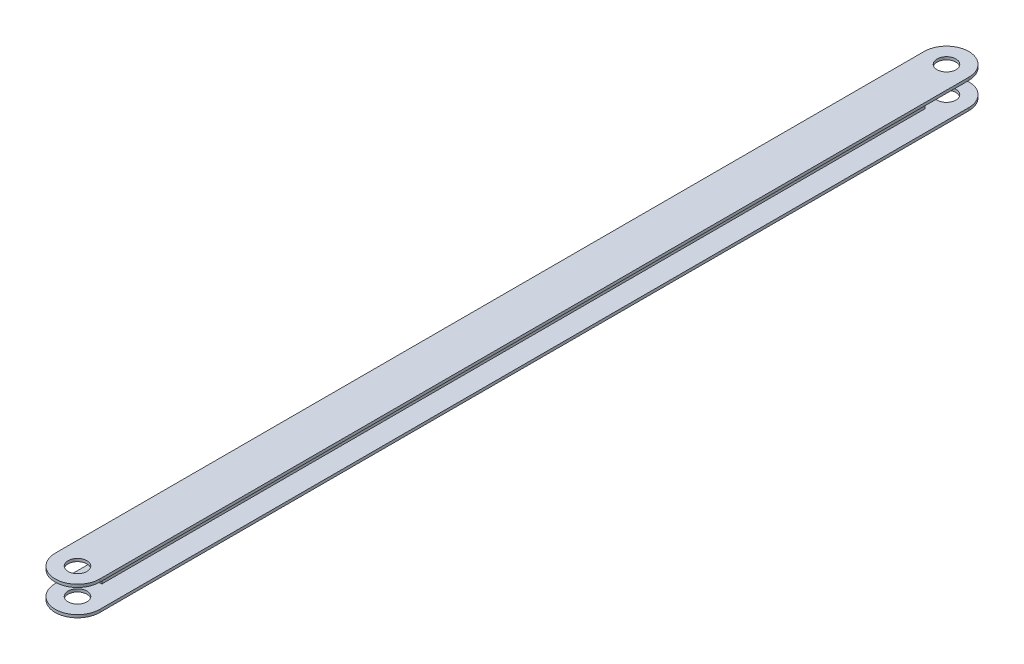
SolidWorks part; units mm, degrees
ref_plane "Front Plane" through (0, 0, 0) normal (0, 0, 1) x (1, 0, 0)
ref_plane "Top Plane" through (0, 0, 0) normal (0, 1, 0) x (1, 0, 0)
ref_plane "Right Plane" through (0, 0, 0) normal (1, 0, 0) x (0, 0, -1)
sketch "Sketch1" plane through (0, 0, 0) normal (0, 0, 1) x (1, 0, 0)
  line L0 (0, 0) -> (0, -5.6)
  line L1 (-0.6, 5) -> (0.6, 5)
  line L2 (-0.6, 5) -> (-0.6, -5)
  line L3 (-0.6, -5) -> (0.6, -5)
  line L4 (0.6, 5) -> (0.6, -5)
  line L5 (-0.6, 5) -> (0.6, -5) construction
  line L6 (-0.6, -5) -> (0.6, 5) construction
  line L7 (-9.5, -5) -> (9.5, -5)
  line L8 (-9.5, -5) -> (-9.5, -6.2)
  line L9 (-9.5, -6.2) -> (9.5, -6.2)
  line L10 (9.5, -5) -> (9.5, -6.2)
  line L11 (-9.5, -5) -> (9.5, -6.2) construction
  line L12 (-9.5, -6.2) -> (9.5, -5) construction
  line L13 (0, 0) -> (6.3315, 0) construction
  line L14 (-9.5, 6.2) -> (9.5, 5) construction
  line L15 (-9.5, 5) -> (9.5, 6.2) construction
  line L16 (9.5, 5) -> (9.5, 6.2)
  line L17 (-9.5, 6.2) -> (9.5, 6.2)
  line L18 (-9.5, 5) -> (-9.5, 6.2)
  line L19 (-9.5, 5) -> (9.5, 5)
  line L20 (-0.6, 5) -> (0.6, 5)
  point P0 (0, 0)
  point P6 (0, -5.6)
  point P19 (0, 5.6)
  dimension "D1" = 10
  dimension "D2" = 1.2
  dimension "D3" = 19
  dimension "D4" = 1.2
extrude "Boss-Extrude1" add sketch "Sketch1" along normal blind 389 contours L18 L19 L1 L16 L17 | L4 L1 L2 L3 | L10 L7 L3 L8 L9 region at (0, 5.6, 0) region at (0, 4.8993, 0) region at (-0.3, -5.1904, 0)
sketch "Sketch3" plane through (0, 6.2, 0) normal (0, 1, 0) x (1, 0, 0)
  line L0 (-9.5, 0) -> (9.5, 0) construction
  line L1 (-14.5, -9.5) -> (-9.5, -9.5)
  line L2 (9.5, -9.5) -> (14.5, -9.5)
  line L3 (9.5, -389) -> (9.5, 0) construction
  line L4 (-9.5, -389) -> (-9.5, 0) construction
  line L12 (9.5, -9.5) -> (4, -9.5)
  line L13 (-4, -9.5) -> (-9.5, -9.5)
  line L16 (-19.5, -399) -> (19.5, -399)
  line L17 (19.5, -399) -> (19.5, 10)
  line L18 (19.5, 10) -> (-19.5, 10)
  line L19 (-19.5, 10) -> (-19.5, -399)
  line L20 (-19.5, -399) -> (19.5, -399)
  line L21 (19.5, -399) -> (19.5, 10)
  line L22 (19.5, 10) -> (-19.5, 10)
  line L23 (-19.5, 10) -> (-19.5, -399)
  arc A0 (9.5, -9.5) -> (-9.5, -9.5) centre (0, -9.5) ccw
  circle A1 centre (0, -9.5) radius 4
  arc A2 (14.5, -9.5) -> (-14.5, -9.5) centre (0, -9.5) ccw
  line M5 (9.5, 0) -> (-9.5, 0)
  line M6 (-9.5, 0) -> (-9.5, -389)
  line M8 (9.5, -389) -> (9.5, 0)
  dimension "D1" = 9.5
  dimension "D2" = 10
  dimension "D3" = 5
ref_plane "Plane4" through (0, 0, 194.5) normal (0, 0, 1) x (1, 0, 0)
extrude "Cut-Extrude2" cut sketch "Sketch3" along direction (0, 1, 0) on the side against the normal blind 370 contours A0 M5 M6 | A0 M8 M5 | L2 A2 L1 M6 M5 M8 | A1 region at (0, 6.2, -4.6758) region at (-7.378, 6.2, 2.122) region at (0, 6.2, 9.5) region at (7.378, 6.2, 2.122)
mirror "Mirror1" about plane through (0, 0, 194.5) normal (0, 0, 1) of "Cut-Extrude2"
sketch "Sketch6" plane through (-0.6, 0, 0) normal (-1, 0, 0) x (0, 0, 1)
  line L0 (379.5, -5) -> (9.5, -5) construction
  line L1 (19.25, -5) -> (-0.25, -5)
  line L2 (19.25, -5) -> (19.25, 5)
  line L3 (19.25, 5) -> (-0.25, 5)
  line L4 (-0.25, -5) -> (-0.25, 5)
  line L5 (19.25, -5) -> (-0.25, 5) construction
  line L6 (19.25, 5) -> (-0.25, -5) construction
  line L7 (9.5, 5) -> (9.5, -5)
  point P0 (9.5, 0)
  line M3 (388.981, 5) -> (383.4547, 5)
  dimension "D1" = 19.5
extrude "Cut-Extrude4" cut sketch "Sketch6" along direction (1, 0, 0) on the side against the normal blind 370 contours L7 L3 L1 | L7 L1 L2 M3 region at (-0.6, 0, 14.375) region at (-0.6, 0, 4.625)
mirror "Mirror2" about plane through (0, 0, 194.5) normal (0, 0, 1) of "Cut-Extrude4"
